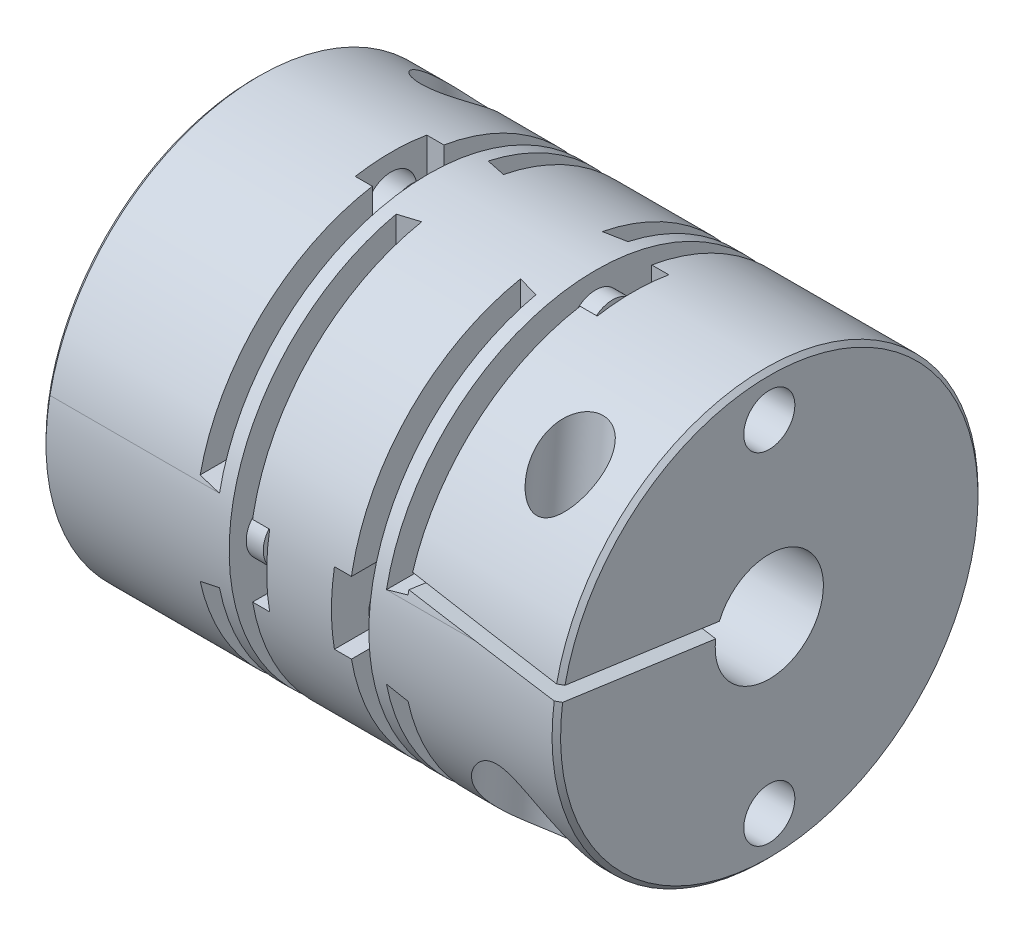
SolidWorks part; units mm, degrees
ref_plane "Front Plane" through (0, 0, 0) normal (0, 0, 1) x (1, 0, 0)
ref_plane "Top Plane" through (0, 0, 0) normal (0, 1, 0) x (1, 0, 0)
ref_plane "Right Plane" through (0, 0, 0) normal (1, 0, 0) x (0, 0, -1)
ref_plane "Plane1" through (0, 0, 0) normal (0, 0, 1) x (1, 0, 0)
sketch "Sketch1" plane through (0, 0, 0) normal (0, 0, 1) x (1, 0, 0)
  line L0 (0, 3.175) -> (9, 3.175)
  line L1 (9, 3.175) -> (9, 5.2)
  line L2 (9, 5.2) -> (21.2, 5.2)
  line L3 (21.2, 5.2) -> (21.2, 3.175)
  line L4 (21.2, 3.175) -> (30.2, 3.175)
  line L5 (30.2, 3.175) -> (30.2, 12.25)
  line L6 (30.2, 12.25) -> (29.95, 12.5)
  line L7 (29.95, 12.5) -> (0.25, 12.5)
  line L8 (0.25, 12.5) -> (0, 12.25)
  line L9 (0, 12.25) -> (0, 3.175)
  line L10 (30.2, 0) -> (0, 0) construction
revolve "Revolve1" add sketch "Sketch1" angle 360 about L10 reverse direction yes
ref_plane "Plane2" through (0, 0, 0) normal (0, -0.1392, 0.9903) x (1, 0, 0)
sketch "Sketch2" plane through (0, 0, 0) normal (0, -0.1392, 0.9903) x (1, 0, 0)
  line L0 (-1.3514, 1.4356) -> (-1.24, 0.6434)
  line L1 (-1.24, 0.6434) -> (10.2, 2.2512)
  line L2 (10.2, 2.2512) -> (10.2, 3.059)
  line L3 (10.2, 3.059) -> (-1.3514, 1.4356)
extrude "Cut-Extrude1" cut sketch "Sketch2" against normal blind 12.5
ref_plane "Plane3" through (0, 0, 0) normal (0, 0.1392, 0.9903) x (1, 0, 0)
sketch "Sketch3" plane through (0, 0, 0) normal (0, 0.1392, 0.9903) x (1, 0, 0)
  line L0 (20, 1.3791) -> (30.2, 0)
  line L1 (30.2, 0) -> (30.3072, 0.7928)
  line L2 (30.3072, 0.7928) -> (20, 2.1864)
  line L3 (20, 2.1864) -> (20, 1.3791)
extrude "Cut-Extrude2" cut sketch "Sketch3" along normal blind 12.5
ref_plane "Plane4" through (4, 0, 0) normal (1, 0, 0) x (0, 0, -1)
sketch "Sketch4" plane through (4, 0, 0) normal (1, 0, 0) x (0, 0, -1)
  line L0 (7.3782, 13.1933) -> (9.1714, 13.3501)
  line L1 (9.1714, 13.3501) -> (9.825, 5.8787)
  line L2 (9.825, 5.8787) -> (9.5262, 5.8525)
  line L3 (9.5262, 5.8525) -> (9.2803, 5.5595)
  line L4 (9.2803, 5.5595) -> (9.6689, 1.1175)
  line L5 (9.6689, 1.1175) -> (9.9619, 0.8716)
  line L6 (9.9619, 0.8716) -> (10.2234, -2.117)
  line L7 (10.2234, -2.117) -> (11.8671, -1.9732)
  line L8 (11.8671, -1.9732) -> (12.6951, -11.4371)
  line L9 (12.6951, -11.4371) -> (9.5571, -11.7116)
  line L10 (9.5571, -11.7116) -> (7.3782, 13.1933)
  line L11 (9.5571, -11.7116) -> (7.3782, 13.1933) construction
revolve "Cut-Revolve1" cut sketch "Sketch4" angle 360 about L11 reverse direction yes
ref_plane "Plane5" through (26.2, 0, 0) normal (1, 0, 0) x (0, 0, -1)
sketch "Sketch5" plane through (26.2, 0, 0) normal (1, 0, 0) x (0, 0, -1)
  line L0 (-7.3782, 13.1933) -> (-5.5851, 13.0364)
  line L1 (-5.5851, 13.0364) -> (-6.2387, 5.5649)
  line L2 (-6.2387, 5.5649) -> (-6.5376, 5.5911)
  line L3 (-6.5376, 5.5911) -> (-6.8306, 5.3452)
  line L4 (-6.8306, 5.3452) -> (-7.1495, 1.7001)
  line L5 (-7.1495, 1.7001) -> (-6.9036, 1.407)
  line L6 (-6.9036, 1.407) -> (-7.2348, -2.3785)
  line L7 (-7.2348, -2.3785) -> (-5.5911, -2.5223)
  line L8 (-5.5911, -2.5223) -> (-6.4191, -11.9862)
  line L9 (-6.4191, -11.9862) -> (-9.5571, -11.7116)
  line L10 (-9.5571, -11.7116) -> (-7.3782, 13.1933)
  line L11 (-9.5571, -11.7116) -> (-7.3782, 13.1933) construction
revolve "Cut-Revolve2" cut sketch "Sketch5" angle 360 about L11 reverse direction yes
ref_plane "Plane6" through (0, 0, 0) normal (0, 0, 1) x (1, 0, 0)
sketch "Sketch6" plane through (0, 0, 0) normal (0, 0, 1) x (1, 0, 0)
  line L0 (9, 13) -> (9, 2.7)
  line L1 (9, 2.7) -> (10.2, 2.4)
  line L2 (10.2, 2.4) -> (10.2, 12.5)
  line L3 (10.2, 12.5) -> (20, 12.5)
  line L4 (20, 12.5) -> (20, 2.4)
  line L5 (20, 2.4) -> (21.2, 2.7)
  line L6 (21.2, 2.7) -> (21.2, 13)
  line L7 (21.2, 13) -> (9, 13)
extrude "Cut-Extrude3" cut sketch "Sketch6" against normal blind 12.5 and the other way blind 12.5
ref_plane "Plane7" through (0, 0, 0) normal (0, 0, 1) x (1, 0, 0)
sketch "Sketch7" plane through (0, 0, 0) normal (0, 0, 1) x (1, 0, 0)
  line L0 (9, -13) -> (21.2, -13)
  line L1 (21.2, -13) -> (21.2, -2.7)
  line L2 (21.2, -2.7) -> (20, -2.4)
  line L3 (20, -2.4) -> (20, -12.5)
  line L4 (20, -12.5) -> (10.2, -12.5)
  line L5 (10.2, -12.5) -> (10.2, -2.4)
  line L6 (10.2, -2.4) -> (9, -2.7)
  line L7 (9, -2.7) -> (9, -13)
extrude "Cut-Extrude4" cut sketch "Sketch7" against normal blind 12.5 and the other way blind 12.5
ref_plane "Plane8" through (0, 0, 0) normal (0, 1, 0) x (-1, 0, 0)
sketch "Sketch8" plane through (0, 0, 0) normal (0, 1, 0) x (-1, 0, 0)
  line L0 (-11, -13) -> (-11, -2.7)
  line L1 (-11, -2.7) -> (-12.2, -2.4)
  line L2 (-12.2, -2.4) -> (-12.2, -12.5)
  line L3 (-12.2, -12.5) -> (-18, -12.5)
  line L4 (-18, -12.5) -> (-18, -2.4)
  line L5 (-18, -2.4) -> (-19.2, -2.7)
  line L6 (-19.2, -2.7) -> (-19.2, -13)
  line L7 (-19.2, -13) -> (-11, -13)
extrude "Cut-Extrude5" cut sketch "Sketch8" against normal blind 12.5 and the other way blind 12.5
ref_plane "Plane9" through (0, 0, 0) normal (0, 1, 0) x (-1, 0, 0)
sketch "Sketch9" plane through (0, 0, 0) normal (0, 1, 0) x (-1, 0, 0)
  line L0 (-11, 13) -> (-19.2, 13)
  line L1 (-19.2, 13) -> (-19.2, 2.7)
  line L2 (-19.2, 2.7) -> (-18, 2.4)
  line L3 (-18, 2.4) -> (-18, 12.5)
  line L4 (-18, 12.5) -> (-12.2, 12.5)
  line L5 (-12.2, 12.5) -> (-12.2, 2.4)
  line L6 (-12.2, 2.4) -> (-11, 2.7)
  line L7 (-11, 2.7) -> (-11, 13)
extrude "Cut-Extrude6" cut sketch "Sketch9" against normal blind 12.5 and the other way blind 12.5
ref_plane "Plane10" through (18, 0, 0) normal (1, 0, 0) x (0, 0, -1)
sketch "Sketch10" plane through (18, 0, 0) normal (1, 0, 0) x (0, 0, -1)
  line L0 (-12.5, -2.1) -> (-10, -2.1)
  line L1 (-10, 2.1) -> (-12.5, 2.1)
  line L2 (-12.5, 2.1) -> (-12.5, -2.1)
  arc A0 (-10, -2.1) -> (-10, 2.1) centre (-10, 0) ccw
extrude "Cut-Extrude7" cut sketch "Sketch10" against normal blind 1
ref_plane "Plane11" through (18, 0, 0) normal (1, 0, 0) x (0, 0, -1)
sketch "Sketch11" plane through (18, 0, 0) normal (1, 0, 0) x (0, 0, -1)
  line L0 (10, -2.1) -> (12.5, -2.1)
  line L1 (12.5, -2.1) -> (12.5, 2.1)
  line L2 (12.5, 2.1) -> (10, 2.1)
  arc A0 (10, 2.1) -> (10, -2.1) centre (10, 0) ccw
extrude "Cut-Extrude8" cut sketch "Sketch11" against normal blind 1
ref_plane "Plane12" through (12.2, 0, 0) normal (1, 0, 0) x (0, 0, -1)
sketch "Sketch12" plane through (12.2, 0, 0) normal (1, 0, 0) x (0, 0, -1)
  line L0 (-12.5, -2.1) -> (-10, -2.1)
  line L1 (-10, 2.1) -> (-12.5, 2.1)
  line L2 (-12.5, 2.1) -> (-12.5, -2.1)
  arc A0 (-10, -2.1) -> (-10, 2.1) centre (-10, 0) ccw
extrude "Cut-Extrude9" cut sketch "Sketch12" along normal blind 1
ref_plane "Plane13" through (12.2, 0, 0) normal (1, 0, 0) x (0, 0, -1)
sketch "Sketch13" plane through (12.2, 0, 0) normal (1, 0, 0) x (0, 0, -1)
  line L0 (10, -2.1) -> (12.5, -2.1)
  line L1 (12.5, -2.1) -> (12.5, 2.1)
  line L2 (12.5, 2.1) -> (10, 2.1)
  arc A0 (10, 2.1) -> (10, -2.1) centre (10, 0) ccw
extrude "Cut-Extrude10" cut sketch "Sketch13" along normal blind 1
ref_plane "Plane14" through (9, 0, 0) normal (1, 0, 0) x (0, 0, -1)
sketch "Sketch14" plane through (9, 0, 0) normal (1, 0, 0) x (0, 0, -1)
  line L0 (2.1, 10) -> (2.1, 12.5)
  line L1 (2.1, 12.5) -> (-2.1, 12.5)
  line L2 (-2.1, 12.5) -> (-2.1, 10)
  arc A0 (-2.1, 10) -> (2.1, 10) centre (0, 10) ccw
extrude "Cut-Extrude11" cut sketch "Sketch14" against normal blind 1
ref_plane "Plane15" through (9, 0, 0) normal (1, 0, 0) x (0, 0, -1)
sketch "Sketch15" plane through (9, 0, 0) normal (1, 0, 0) x (0, 0, -1)
  line L0 (-2.1, -10) -> (-2.1, -12.5)
  line L1 (-2.1, -12.5) -> (2.1, -12.5)
  line L2 (2.1, -12.5) -> (2.1, -10)
  arc A0 (2.1, -10) -> (-2.1, -10) centre (0, -10) ccw
extrude "Cut-Extrude12" cut sketch "Sketch15" against normal blind 1
ref_plane "Plane16" through (21.2, 0, 0) normal (1, 0, 0) x (0, 0, -1)
sketch "Sketch16" plane through (21.2, 0, 0) normal (1, 0, 0) x (0, 0, -1)
  line L0 (2.1, 10) -> (2.1, 12.5)
  line L1 (2.1, 12.5) -> (-2.1, 12.5)
  line L2 (-2.1, 12.5) -> (-2.1, 10)
  arc A0 (-2.1, 10) -> (2.1, 10) centre (0, 10) ccw
extrude "Cut-Extrude13" cut sketch "Sketch16" along normal blind 1
ref_plane "Plane17" through (21.2, 0, 0) normal (1, 0, 0) x (0, 0, -1)
sketch "Sketch17" plane through (21.2, 0, 0) normal (1, 0, 0) x (0, 0, -1)
  line L0 (-2.1, -10) -> (-2.1, -12.5)
  line L1 (-2.1, -12.5) -> (2.1, -12.5)
  line L2 (2.1, -12.5) -> (2.1, -10)
  arc A0 (2.1, -10) -> (-2.1, -10) centre (0, -10) ccw
extrude "Cut-Extrude14" cut sketch "Sketch17" along normal blind 1
ref_plane "Plane18" through (11, 0, 0) normal (1, 0, 0) x (0, 0, -1)
sketch "Sketch18" plane through (11, 0, 0) normal (1, 0, 0) x (0, 0, -1)
  circle A0 centre (-10, 0) radius 1.5
extrude "Boss-Extrude1" add sketch "Sketch18" along normal blind 1
ref_plane "Plane19" through (11, 0, 0) normal (1, 0, 0) x (0, 0, -1)
sketch "Sketch19" plane through (11, 0, 0) normal (1, 0, 0) x (0, 0, -1)
  circle A0 centre (10, 0) radius 1.5
extrude "Boss-Extrude2" add sketch "Sketch19" along normal blind 1
ref_plane "Plane20" through (10.2, 0, 0) normal (1, 0, 0) x (0, 0, -1)
sketch "Sketch20" plane through (10.2, 0, 0) normal (1, 0, 0) x (0, 0, -1)
  circle A0 centre (0, 10) radius 1.5
extrude "Boss-Extrude3" add sketch "Sketch20" against normal blind 1
ref_plane "Plane21" through (10.2, 0, 0) normal (1, 0, 0) x (0, 0, -1)
sketch "Sketch21" plane through (10.2, 0, 0) normal (1, 0, 0) x (0, 0, -1)
  circle A0 centre (0, -10) radius 1.5
extrude "Boss-Extrude4" add sketch "Sketch21" against normal blind 1
ref_plane "Plane22" through (19.2, 0, 0) normal (1, 0, 0) x (0, 0, -1)
sketch "Sketch22" plane through (19.2, 0, 0) normal (1, 0, 0) x (0, 0, -1)
  circle A0 centre (-10, 0) radius 1.5
extrude "Boss-Extrude5" add sketch "Sketch22" against normal blind 1
ref_plane "Plane23" through (19.2, 0, 0) normal (1, 0, 0) x (0, 0, -1)
sketch "Sketch23" plane through (19.2, 0, 0) normal (1, 0, 0) x (0, 0, -1)
  circle A0 centre (10, 0) radius 1.5
extrude "Boss-Extrude6" add sketch "Sketch23" against normal blind 1
ref_plane "Plane24" through (20, 0, 0) normal (1, 0, 0) x (0, 0, -1)
sketch "Sketch24" plane through (20, 0, 0) normal (1, 0, 0) x (0, 0, -1)
  circle A0 centre (0, 10) radius 1.5
extrude "Boss-Extrude7" add sketch "Sketch24" along normal blind 1
ref_plane "Plane25" through (20, 0, 0) normal (1, 0, 0) x (0, 0, -1)
sketch "Sketch25" plane through (20, 0, 0) normal (1, 0, 0) x (0, 0, -1)
  circle A0 centre (0, -10) radius 1.5
extrude "Boss-Extrude8" add sketch "Sketch25" along normal blind 1
ref_plane "Plane26" through (0, 0, 0) normal (1, 0, 0) x (0, 0, -1)
sketch "Sketch26" plane through (0, 0, 0) normal (1, 0, 0) x (0, 0, -1)
  circle A0 centre (0, 10) radius 1.5
extrude "Cut-Extrude15" cut sketch "Sketch26" along normal blind 9
ref_plane "Plane27" through (0, 0, 0) normal (1, 0, 0) x (0, 0, -1)
sketch "Sketch27" plane through (0, 0, 0) normal (1, 0, 0) x (0, 0, -1)
  circle A0 centre (0, -10) radius 1.5
extrude "Cut-Extrude16" cut sketch "Sketch27" along normal blind 9
ref_plane "Plane28" through (30.2, 0, 0) normal (1, 0, 0) x (0, 0, -1)
sketch "Sketch28" plane through (30.2, 0, 0) normal (1, 0, 0) x (0, 0, -1)
  circle A0 centre (0, 10) radius 1.5
extrude "Cut-Extrude17" cut sketch "Sketch28" against normal blind 9
ref_plane "Plane29" through (30.2, 0, 0) normal (1, 0, 0) x (0, 0, -1)
sketch "Sketch29" plane through (30.2, 0, 0) normal (1, 0, 0) x (0, 0, -1)
  circle A0 centre (0, -10) radius 1.5
extrude "Cut-Extrude18" cut sketch "Sketch29" against normal blind 9
